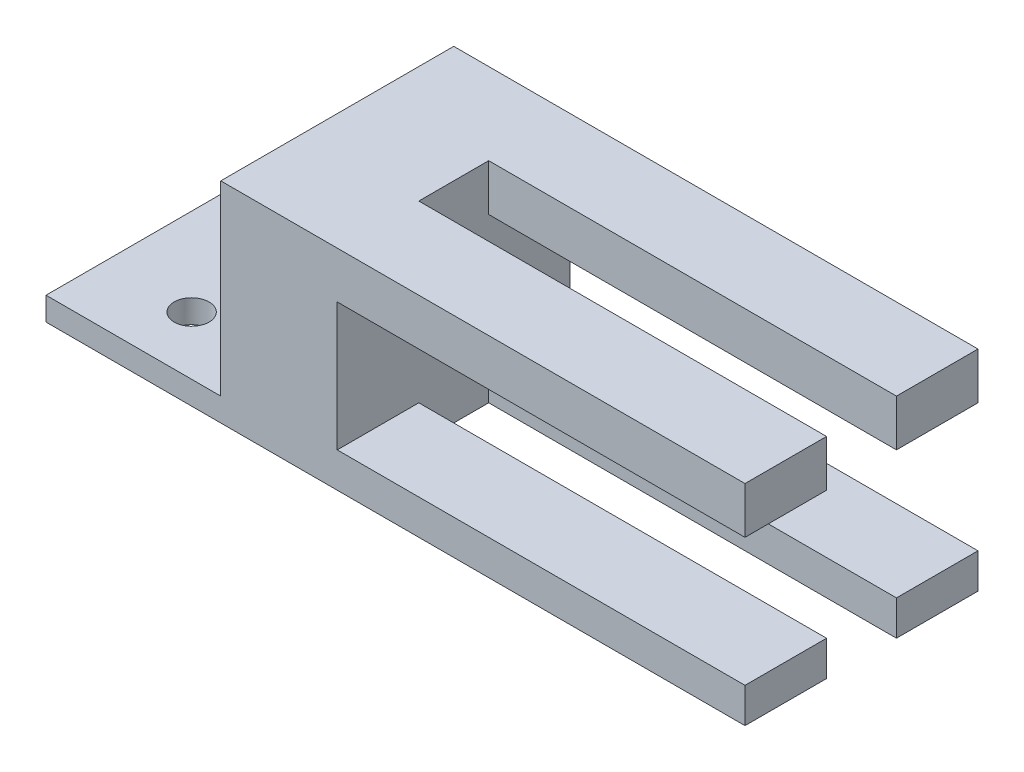
SolidWorks part; units mm, degrees
ref_plane "Front Plane" through (0, 0, 0) normal (0, 0, 1) x (1, 0, 0)
ref_plane "Top Plane" through (0, 0, 0) normal (0, 1, 0) x (1, 0, 0)
ref_plane "Right Plane" through (0, 0, 0) normal (1, 0, 0) x (0, 0, -1)
sketch "Sketch1" plane through (0, 0, 0) normal (0, 0, 1) x (1, 0, 0)
  line L0 (0, 36.1346) -> (0, -32.9015) construction
  line L2 (-5, 15) -> (5, 15)
  line L3 (-5, 15) -> (-5, -3)
  line L4 (-5, -3) -> (5, -3)
  line L5 (5, 15) -> (5, -3)
  dimension "D1" = 5
  dimension "D2" = 5
  dimension "D3" = 18
  dimension "D4" = 15
extrude "Boss-Extrude1" add sketch "Sketch1" along normal blind 10 and the other way blind 10
sketch "Sketch2" plane through (0, 0, 0) normal (1, 0, 0) x (0, 0, -1)
  line L0 (0, 39.4604) -> (0, -37.7676) construction
  line L1 (10, -3) -> (10, 15) construction
  line L2 (-10, -3) -> (10, -3)
  line L3 (-10, -3) -> (-10, -1)
  line L4 (-10, -1) -> (10, -1)
  line L5 (10, -3) -> (10, -1)
  dimension "D1" = 2
extrude "Boss-Extrude2" add sketch "Sketch2" against normal blind 20
sketch "Sketch3" plane through (0, 0, 0) normal (1, 0, 0) x (0, 0, -1)
  line L0 (10, 15) -> (-10, 15) construction
  line L1 (-10, 15) -> (-3, 15)
  line L2 (-10, 15) -> (-10, 11)
  line L3 (-10, 11) -> (-3, 11)
  line L4 (-3, 15) -> (-3, 11)
  line L5 (-10, -3) -> (-10, 15) construction
  line L6 (-10, 0) -> (-3, 0)
  line L7 (-10, 0) -> (-10, -3)
  line L8 (-10, -3) -> (-3, -3)
  line L9 (-3, 0) -> (-3, -3)
  line L10 (0, 17.8503) -> (0, -15.9277) construction
  line L11 (10, -3) -> (3, -3)
  line L12 (10, 0) -> (10, -3)
  line L13 (3, 0) -> (3, -3)
  line L14 (10, 0) -> (3, 0)
  line L15 (10, 11) -> (3, 11)
  line L16 (3, 15) -> (3, 11)
  line L17 (10, 15) -> (3, 15)
  line L18 (10, 15) -> (10, 11)
  line L19 (10, -3) -> (-10, -3) construction
  dimension "D1" = 7
  dimension "D2" = 4
  dimension "D3" = 7
  dimension "D5" = 15
extrude "Boss-Extrude3" add sketch "Sketch3" along normal blind 40
sketch "Sketch7" plane through (0, 0, 0) normal (0, 1, 0) x (1, 0, 0)
  line L0 (-23.4588, 0) -> (13.7691, 0) construction
  line L1 (-12.5, 10) -> (-12.5, -10) construction
  line L2 (-20, 10) -> (-5, 10) construction
  line L3 (-20, -10) -> (-5, -10) construction
  circle A0 centre (-12.5, 5) radius 1.5
  circle A1 centre (-12.5, -5) radius 1.5
  dimension "D1" = 3
  dimension "D2" = 5
extrude "Cut-Extrude2" cut sketch "Sketch7" against normal blind 10
